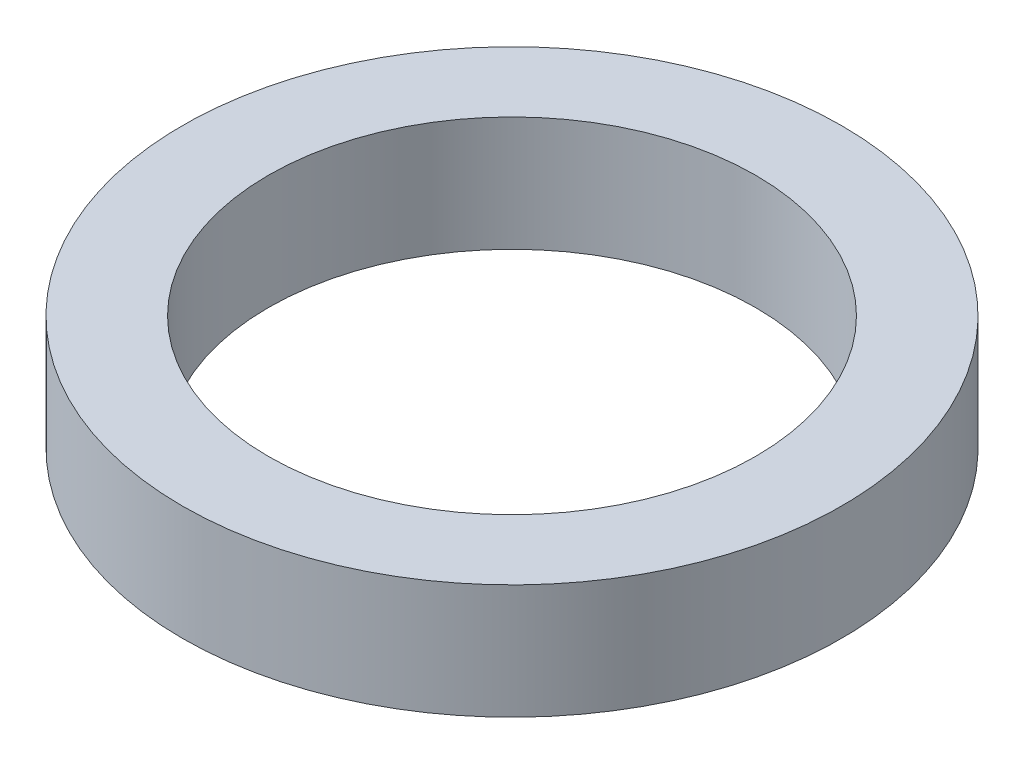
SolidWorks part; units mm, degrees
ref_plane "Front Plane" through (0, 0, 0) normal (0, 0, 1) x (1, 0, 0)
ref_plane "Top Plane" through (0, 0, 0) normal (0, 1, 0) x (1, 0, 0)
ref_plane "Right Plane" through (0, 0, 0) normal (1, 0, 0) x (0, 0, -1)
sketch "Sketch1" plane through (0, 0, 0) normal (0, 1, 0) x (1, 0, 0)
  circle A0 centre (0, 0) radius 57.5
  dimension "FLANGE_OD" = 115
extrude "Boss-Extrude1" add sketch "Sketch1" along normal blind 20
sketch "Sketch2" plane through (0, 0, 0) normal (0, 1, 0) x (1, 0, 0)
  circle A0 centre (0, 0) radius 42.5
  dimension "BORE_D" = 85
extrude "Cut-Extrude1" cut sketch "Sketch2" along normal through all
sketch "Sketch3" plane through (0, 20, 0) normal (0, 1, 0) x (1, 0, 0)
  circle A0 centre (0, 0) radius 25.0474 construction
  circle A1 centre (-25.0474, 0) radius 1.5245
  dimension "BOLT_D" = 3.049
  dimension "BOLT_PCD" = 50.0947
extrude "Cut-Extrude2" cut sketch "Sketch3" against normal blind 15.5708 rebuild error yes
pattern_circular "CirPattern1" count 4 over 360 rebuild error yes
